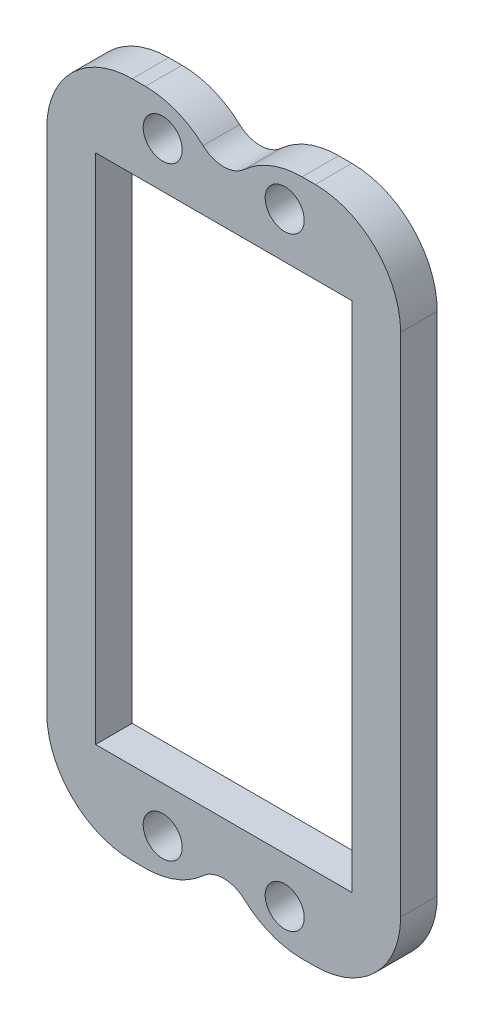
SolidWorks part; units mm, degrees
material "MDF"
ref_plane "Plano frontal" through (0, 0, 0) normal (0, 0, 1) x (1, 0, 0)
ref_plane "Plano superior" through (0, 0, 0) normal (0, 1, 0) x (1, 0, 0)
ref_plane "Plano direito" through (0, 0, 0) normal (1, 0, 0) x (0, 0, -1)
sketch "Esboço1" plane through (0, 0, 0) normal (0, 0, 1) x (1, 0, 0)
  line L5 (-10.5, -21) -> (10.5, -21)
  line L6 (-10.5, -21) -> (-10.5, 21)
  line L7 (-10.5, 21) -> (10.5, 21)
  line L8 (10.5, -21) -> (10.5, 21)
  line L9 (0, 21) -> (0, -21) construction
  line L10 (-10.5, 0) -> (10.5, 0) construction
  line L11 (-14.5, -27.75) -> (14.5, -27.75)
  line L12 (-14.5, -27.75) -> (-14.5, 27.75)
  line L13 (-14.5, 27.75) -> (14.5, 27.75)
  line L14 (14.5, -27.75) -> (14.5, 27.75)
  line L15 (0, 27.75) -> (0, -27.75) construction
  line L16 (-14.5, 0) -> (14.5, 0) construction
  circle A6 centre (-5, -24.75) radius 1.6
  circle A7 centre (5, -24.75) radius 1.6
  circle A8 centre (5, 24.75) radius 1.6
  circle A9 centre (-5, 24.75) radius 1.6
  arc A10 (-2.5, 27.75) -> (2.5, 27.75) centre (0, 27.75) ccw
  arc A11 (-2.5, -27.75) -> (2.5, -27.75) centre (0, -27.75) cw
  point P0 (0, 0)
  point P4 (0, 0)
  dimension "D1" = 10
  dimension "D2" = 49.5
  dimension "D7" = 4
  dimension "D8" = 2.5
  dimension "D3" = 3.2
  dimension "D4" = 3
  dimension "D5" = 42
  dimension "D6" = 21
extrude "Ressalto-extrusão1" add sketch "Esboço1" along normal blind 3 contours L11 L14 L13 L12 A7 A6 L8 L5 L6 L7 A8 A9 region at (-13.8738, 0, 0)
fillet "Filete1" radius 7 8 edges at (14.5, -27.75, 1.5) (-14.5, -27.75, 1.5) (-14.5, 27.75, 1.5) (14.5, 27.75, 1.5) (2.5, -27.75, 1.5) (-2.5, -27.75, 1.5) (2.5, 27.75, 1.5) (-2.5, 27.75, 1.5)
